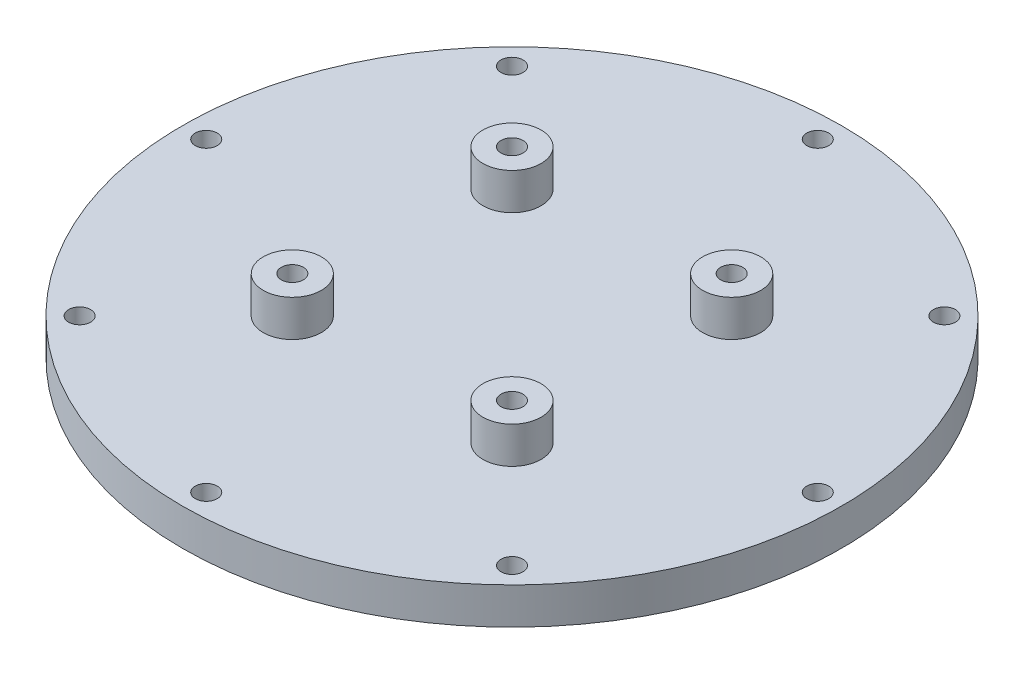
SolidWorks part; units mm, degrees
material "6061-T6 (SS)"
ref_plane "Front Plane" through (0, 0, 0) normal (0, 0, 1) x (1, 0, 0)
ref_plane "Top Plane" through (0, 0, 0) normal (0, 1, 0) x (1, 0, 0)
ref_plane "Right Plane" through (0, 0, 0) normal (1, 0, 0) x (0, 0, -1)
sketch "Sketch1" plane through (0, 0, 0) normal (0, 1, 0) x (1, 0, 0)
  circle A0 centre (0, 0) radius 45
  circle A1 centre (0, 41.75) radius 1.5
  circle A2 centre (29.5217, 29.5217) radius 1.5
  circle A3 centre (41.75, 0) radius 1.5
  circle A4 centre (29.5217, -29.5217) radius 1.5
  circle A5 centre (0, -41.75) radius 1.5
  circle A6 centre (-29.5217, -29.5217) radius 1.5
  circle A7 centre (-41.75, 0) radius 1.5
  circle A8 centre (-29.5217, 29.5217) radius 1.5
  point P22 (0, 0)
  dimension "D1" = 8
extrude "Boss-Extrude2" add sketch "Sketch1" along normal blind 5
sketch "Sketch2" plane through (0, 5, 0) normal (0, 1, 0) x (1, 0, 0)
  line L5 (-20, -20) -> (20, 20) construction
  line L6 (-20, 20) -> (20, -20) construction
  circle A0 centre (-10, 10) radius 3.9688
  circle A1 centre (10, 10) radius 3.9687
  circle A2 centre (10, -10) radius 3.9687
  circle A3 centre (-10, -10) radius 3.9688
  point P0 (0, 0)
  dimension "D4" = 2
  dimension "D1" = 40
  dimension "D2" = 40
  dimension "D3" = 2
extrude "Boss-Extrude3" add sketch "Sketch2" along normal blind 5
sketch "Sketch3" plane through (0, 10, 0) normal (0, 1, 0) x (1, 0, 0)
  circle A0 centre (-10, 10) radius 1.5
  circle A1 centre (10, 10) radius 1.5
  circle A2 centre (-10, -10) radius 1.5
  circle A3 centre (10, -10) radius 1.5
extrude "Cut-Extrude1" cut sketch "Sketch3" against normal blind 7
sketch "Sketch4" plane through (0, 0, 0) normal (0, 0, 1) x (1, 0, 0)
  line L1 (-13.9687, 10) -> (13.9688, 10)
  line L2 (-13.9687, 10) -> (-13.9687, 5)
  line L3 (-13.9687, 5) -> (13.9688, 5)
  line L4 (13.9688, 10) -> (13.9688, 5)
extrude "Cut-Extrude2" cut sketch "Sketch4" against normal blind 19 and the other way blind 27
sketch "Sketch5" plane through (0, 5, 0) normal (0, 1, 0) x (1, 0, 0)
  line L1 (-18.5559, 17.7877) -> (19.5015, 17.7877)
  line L2 (-18.5559, 17.7877) -> (-18.5559, -18.615)
  line L3 (-18.5559, -18.615) -> (19.5015, -18.615)
  line L4 (19.5015, 17.7877) -> (19.5015, -18.615)
extrude "Boss-Extrude4" add sketch "Sketch5" against normal blind 4
sketch "Sketch6" plane through (0, 5, 0) normal (0, 1, 0) x (1, 0, 0)
  line L5 (-15, -15) -> (15, 15) construction
  line L6 (-15, 15) -> (15, -15) construction
  circle A0 centre (-15, 15) radius 1.5
  circle A1 centre (-15, 15) radius 3.9687
  circle A2 centre (15, 15) radius 1.5
  circle A3 centre (15, 15) radius 3.9687
  circle A4 centre (15, -15) radius 1.5
  circle A5 centre (15, -15) radius 3.9687
  circle A6 centre (-15, -15) radius 1.5
  circle A7 centre (-15, -15) radius 3.9687
  point P0 (0, 0)
  point P8 (0, 0)
  point P9 (0, 0)
  point P19 (0, 0)
  dimension "D3" = 2
  dimension "D1" = 30
  dimension "D2" = 30
  dimension "D4" = 2
extrude "Boss-Extrude5" add sketch "Sketch6" along normal blind 5
extrude "Cut-Extrude3" cut sketch "Sketch6<2>" against normal blind 2 contours A0 | A2 | A4 | A6 region at (-15, 5, -15) region at (15, 5, -15)
sketch "Sketch6<2>" plane through (0, 5, 0) normal (0, 1, 0) x (1, 0, 0) same geometry as "Sketch6"
